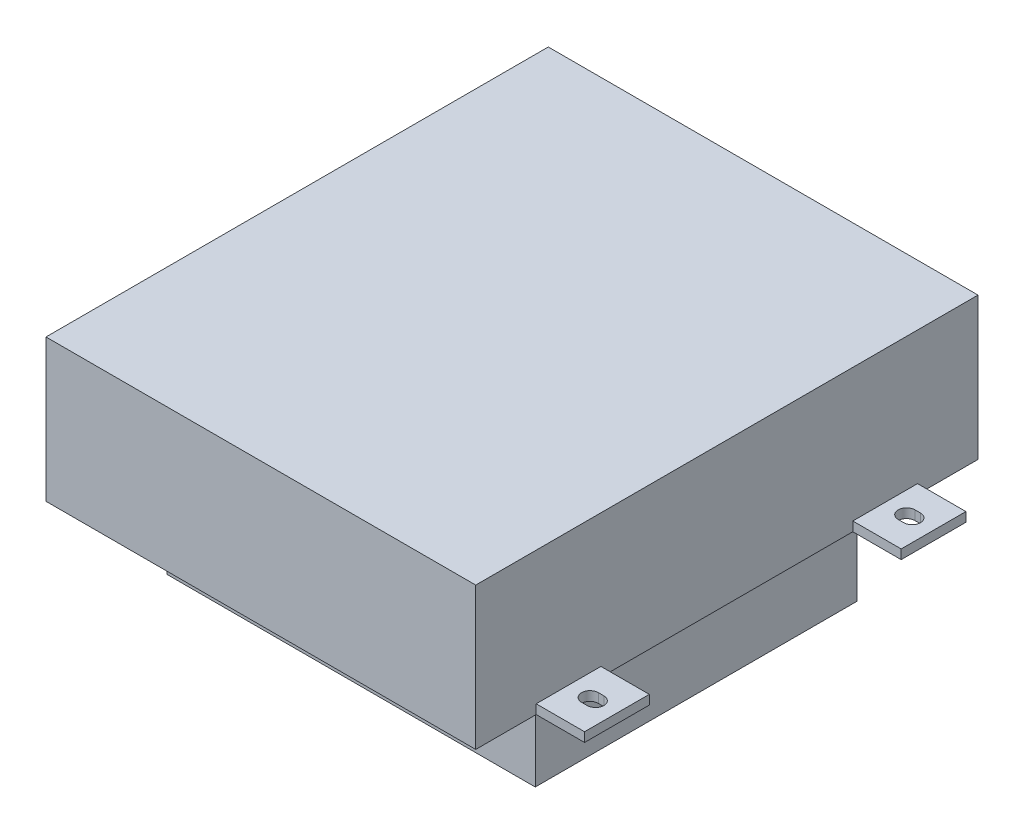
SolidWorks part; units mm, degrees
ref_plane "Front Plane" through (0, 0, 0) normal (0, 0, 1) x (1, 0, 0)
ref_plane "Top Plane" through (0, 0, 0) normal (0, 1, 0) x (1, 0, 0)
ref_plane "Right Plane" through (0, 0, 0) normal (1, 0, 0) x (0, 0, -1)
sketch "Sketch1" plane through (0, 0, 0) normal (0, 1, 0) x (1, 0, 0)
  line L1 (-99, -86.5) -> (99, -86.5)
  line L2 (-99, -86.5) -> (-99, 86.5)
  line L3 (-99, 86.5) -> (99, 86.5)
  line L4 (99, -86.5) -> (99, 86.5)
  line L5 (-99, -86.5) -> (99, 86.5) construction
  line L6 (-99, 86.5) -> (99, -86.5) construction
  line L7 (-115.5, -135) -> (115.5, -135)
  line L8 (-115.5, -135) -> (-115.5, 135)
  line L9 (-115.5, 135) -> (115.5, 135)
  line L10 (115.5, -135) -> (115.5, 135)
  line L11 (-115.5, -135) -> (115.5, 135) construction
  line L12 (-115.5, 135) -> (115.5, -135) construction
  point P0 (0, 0)
  point P6 (0, 0)
  dimension "D1" = 198
  dimension "D2" = 173
  dimension "D3" = 231
  dimension "D4" = 270
extrude "Boss-Extrude1" add sketch "Sketch1" along normal blind 50 contours L1 L4 L3 L2 region at (0, 0, 0)
extrude "Boss-Extrude2" add sketch "Sketch1<3>" along normal blind 76.5302 from surface contours L10 L9 L8 L7 starting at face at (0, 50, 0)
sketch "Sketch1<3>" plane through (0, 0, 0) normal (0, 1, 0) x (1, 0, 0) same geometry as "Sketch1"
sketch "Sketch2" plane through (0, 50, 0) normal (0, -1, 0) x (1, 0, 0)
  line L0 (69.5916, 0) -> (-69.5916, 0) construction
  line L1 (-141.5, -67.7) -> (-115.5, -67.7)
  line L2 (-141.5, -67.7) -> (-141.5, -102.5)
  line L3 (-141.5, -102.5) -> (-115.5, -102.5)
  line L4 (-115.5, -67.7) -> (-115.5, -102.5)
  line L5 (-130, 85.1) -> (-127, 85.1) construction
  line L6 (-115.5, -135) -> (-115.5, 135) construction
  line L7 (115.5, -135) -> (-115.5, -135) construction
  line L8 (-130, -85.1) -> (-127, -85.1) construction
  line L9 (-130, 80.6) -> (-127, 80.6)
  line L10 (-130, -80.6) -> (-127, -80.6)
  line L11 (-130, -89.6) -> (-127, -89.6)
  line L12 (-130, 89.6) -> (-127, 89.6)
  line L13 (-115.5, 67.7) -> (-115.5, 102.5)
  line L14 (-141.5, 102.5) -> (-115.5, 102.5)
  line L15 (-141.5, 67.7) -> (-141.5, 102.5)
  line L16 (-141.5, 67.7) -> (-115.5, 67.7)
  line L17 (0, -69.5916) -> (0, 69.5916) construction
  line L18 (130, 85.1) -> (127, 85.1) construction
  line L19 (130, 80.6) -> (127, 80.6)
  line L20 (130, 89.6) -> (127, 89.6)
  line L21 (130, -85.1) -> (127, -85.1) construction
  line L22 (130, -80.6) -> (127, -80.6)
  line L23 (130, -89.6) -> (127, -89.6)
  line L24 (141.5, 67.7) -> (115.5, 67.7)
  line L25 (141.5, 67.7) -> (141.5, 102.5)
  line L26 (141.5, 102.5) -> (115.5, 102.5)
  line L27 (115.5, 67.7) -> (115.5, 102.5)
  line L28 (115.5, -67.7) -> (115.5, -102.5)
  line L29 (141.5, -102.5) -> (115.5, -102.5)
  line L30 (141.5, -67.7) -> (141.5, -102.5)
  line L31 (141.5, -67.7) -> (115.5, -67.7)
  arc A0 (-130, -80.6) -> (-130, -89.6) centre (-130, -85.1) ccw
  arc A1 (-127, -89.6) -> (-127, -80.6) centre (-127, -85.1) ccw
  arc A2 (-130, 80.6) -> (-130, 89.6) centre (-130, 85.1) cw
  arc A3 (-127, 89.6) -> (-127, 80.6) centre (-127, 85.1) cw
  arc A4 (130, 80.6) -> (130, 89.6) centre (130, 85.1) ccw
  arc A5 (127, 89.6) -> (127, 80.6) centre (127, 85.1) ccw
  arc A6 (130, -80.6) -> (130, -89.6) centre (130, -85.1) cw
  arc A7 (127, -89.6) -> (127, -80.6) centre (127, -85.1) cw
  point P10 (0, 0)
  point P11 (-141.5, -85.1)
  point P12 (-128.5, -85.1)
  point P17 (0, 0)
  point P18 (-128.5, -67.7)
  point P19 (0, 0)
  point P24 (-128.5, 85.1)
  point P37 (128.5, 85.1)
  point P44 (128.5, -85.1)
  dimension "D1" = 34.8
  dimension "D2" = 26
  dimension "D3" = 32.5
  dimension "D4" = 17.4
  dimension "D5" = 3
  dimension "D6" = 9
extrude "Boss-Extrude3" add sketch "Sketch2" against normal blind 5
